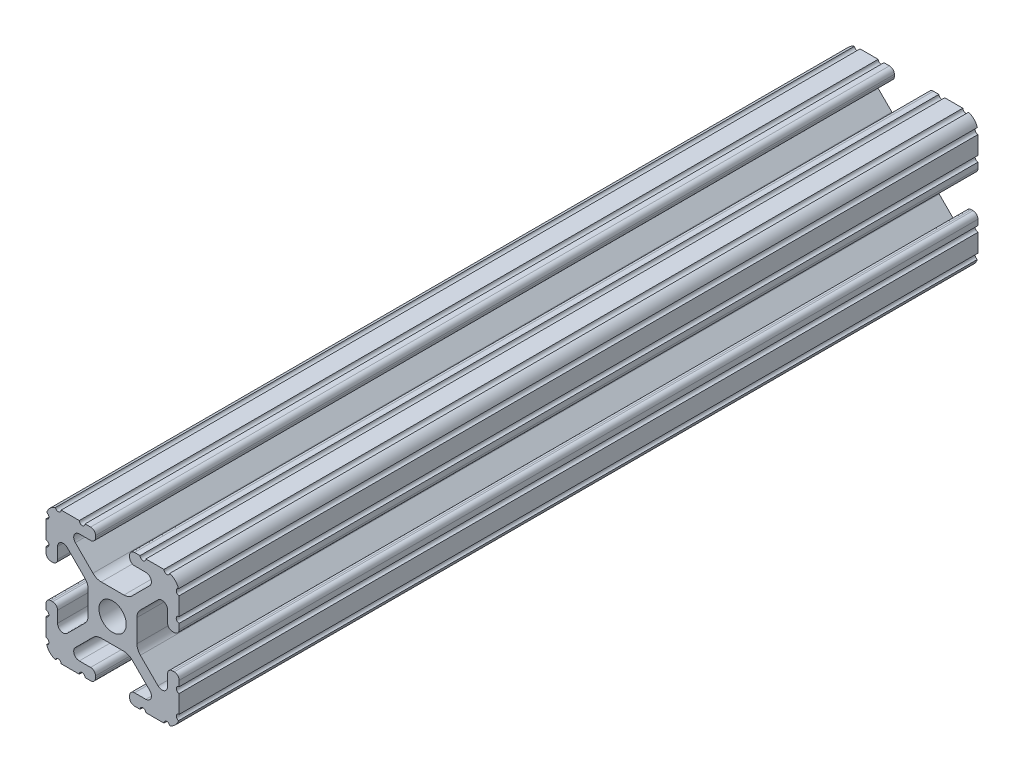
SolidWorks part; units mm, degrees
ref_plane "Front Plane" through (0, 0, 0) normal (0, 0, 1) x (1, 0, 0)
ref_plane "Top Plane" through (0, 0, 0) normal (0, 1, 0) x (1, 0, 0)
ref_plane "Right Plane" through (0, 0, 0) normal (1, 0, 0) x (0, 0, -1)
sketch "Sketch2" plane through (0, 0, 0) normal (0, 0, 1) x (1, 0, 0)
  line L0 (0, 12.7) -> (0, -12.7) construction
  line L1 (-12.7, 0) -> (12.7, 0) construction
  line L2 (3.2512, -12.7) -> (12.7, -12.7)
  line L3 (12.7, -12.7) -> (12.7, -3.2512)
  line L4 (3.2512, -12.7) -> (3.2512, -10.4902)
  line L5 (3.2512, -10.4902) -> (8.9276, -10.4902)
  line L6 (8.9276, -10.4902) -> (3.0856, -4.6482)
  line L7 (0, 0) -> (12.7, -12.7) construction
  line L8 (12.7, -3.2512) -> (10.4902, -3.2512)
  line L9 (10.4902, -3.2512) -> (10.4902, -8.9276)
  line L10 (10.4902, -8.9276) -> (4.6482, -3.0856)
  circle A0 centre (0, 0) radius 2.6035
  arc A1 (6.3485, -10.4902) -> (7.1039, -8.6665) centre (6.3485, -9.4219) ccw construction
  point P8 (0, -4.6482)
  dimension "Center Hole Diameter" = 5.207
  dimension "Rail Height" = 25.4
  dimension "Rail Width" = 25.4
  dimension "T-Slot Width" = 6.5024
  dimension "Slot Inner Width" = 14.8336
  dimension "Thickness" = 2.2098
  dimension "Slot Depth" = 5.842
  dimension "D1" = 2.2098
sketch "Sketch3" plane through (0, 0, 0) normal (1, 0, 0) x (0, 0, -1)
  line L0 (-76.2, -12.7) -> (76.2, -12.7) construction
  line L1 (-68.58, 0) -> (68.58, 0) construction
  dimension "Length" = 152.4
  dimension "D1" = 137.16
sketch "Sketch4" plane through (0, 0, 0) normal (0, 0, 1) x (1, 0, 0)
  line L0 (4.1904, -12.7) -> (10.1173, -12.7)
  line L1 (3.2512, -12.7) -> (12.7, -12.7) construction
  line L2 (3.2512, -12.7) -> (3.2512, -10.4902) construction
  line L3 (3.2512, -10.4902) -> (8.9276, -10.4902) construction
  line L4 (3.2512, -11.4294) -> (3.2512, -11.7608)
  line L5 (4.1904, -10.4902) -> (6.3485, -10.4902)
  line L6 (0, -4.6482) -> (2.164, -4.6482)
  line L7 (8.9276, -10.4902) -> (3.0856, -4.6482) construction
  line L8 (3.7373, -5.2999) -> (7.1039, -8.6665)
  line L9 (12.7, -12.7) -> (12.7, -3.2512) construction
  line L10 (10.4902, -8.9276) -> (4.6482, -3.0856) construction
  line L11 (10.4902, -3.2512) -> (10.4902, -8.9276) construction
  line L12 (10.4902, -6.3485) -> (10.4902, -4.1904)
  line L13 (12.7, -3.2512) -> (10.4902, -3.2512) construction
  line L14 (11.4294, -3.2512) -> (11.7608, -3.2512)
  line L15 (12.7, -4.1904) -> (12.7, -10.1173)
  line L16 (8.6665, -7.1039) -> (5.2999, -3.7373)
  line L17 (4.6482, 0) -> (4.6482, -2.164)
  line L18 (-12.7, 0) -> (12.7, 0) construction
  line L19 (0, -4.6482) -> (0, -2.6035)
  line L20 (0, 12.7) -> (0, -12.7) construction
  line L21 (4.6482, 0) -> (2.6035, 0)
  arc A0 (3.2512, -11.7608) -> (4.1904, -12.7) centre (4.1904, -11.7608) ccw
  arc A2 (3.2512, -11.4294) -> (4.1904, -10.4902) centre (4.1904, -11.4294) cw
  arc A3 (6.3485, -10.4902) -> (7.1039, -8.6665) centre (6.3485, -9.4219) ccw
  arc A4 (2.164, -4.6482) -> (3.7373, -5.2999) centre (2.164, -6.8732) cw
  arc A5 (10.1173, -12.7) -> (12.7, -10.1173) centre (10.1173, -10.1173) ccw
  arc A6 (8.6665, -7.1039) -> (10.4902, -6.3485) centre (9.4219, -6.3485) ccw
  arc A7 (10.4902, -4.1904) -> (11.4294, -3.2512) centre (11.4294, -4.1904) cw
  arc A8 (11.7608, -3.2512) -> (12.7, -4.1904) centre (11.7608, -4.1904) cw
  arc A9 (5.2999, -3.7373) -> (4.6482, -2.164) centre (6.8732, -2.164) cw
  circle A10 centre (0, 0) radius 2.6035 construction
  arc A11 (0, -2.6035) -> (2.6035, 0) centre (0, 0) ccw
  dimension "D1" = 2.5827
  dimension "D2" = 2.225
  dimension "D3" = 0.9392
extrude "Boss-Extrude1" add sketch "Sketch4" along normal mid plane 152.4
sketch "Sketch5" plane through (0, 0, 0) normal (0, 0, 1) x (1, 0, 0)
  line L0 (3.2512, -12.7) -> (12.7, -12.7) construction
  line L1 (4.1904, -10.4902) -> (6.3485, -10.4902) construction
  line L3 (0, 0) -> (12.7, -12.7) construction
  line L4 (6.3485, -10.4902) -> (6.3485, -12.7) construction
  line L5 (8.9276, -10.4902) -> (3.0856, -4.6482) construction
  circle A0 centre (10.3562, -12.7) radius 0.5524
  circle A1 centre (5.796, -12.7) radius 0.5524
  circle A2 centre (12.7, -10.3562) radius 0.5524
  circle A3 centre (12.7, -5.796) radius 0.5524
  point P10 (5.2694, -10.4902)
  point P12 (9.4219, -6.3485)
  dimension "D1" = 1.1049
extrude "Cut-Extrude1" cut sketch "Sketch5" against normal through all both and the other way through all
mirror "Mirror1" about plane through (0, 0, 0) normal (1, 0, 0) of bodies 137 134
mirror "Mirror2" about plane through (0, 0, 0) normal (0, 1, 0) of bodies 135
sketch "Sketch6" plane through (0, 0, 0) normal (0, 1, 0) x (1, 0, 0)
  line L0 (0, 76.2) -> (0, 63.5) construction
  line L1 (0, -76.2) -> (0, -63.5) construction
  line L4 (2.164, 76.2) -> (-2.164, 76.2)
  line L5 (-2.164, 76.2) -> (-2.164, -76.2)
  line L6 (-2.164, -76.2) -> (2.164, -76.2)
  line L7 (2.164, -76.2) -> (2.164, 76.2)
  line L8 (2.164, 76.2) -> (-2.164, 76.2) construction
  line L9 (-2.164, 76.2) -> (-2.164, -76.2) construction
  line L10 (-2.164, -76.2) -> (2.164, -76.2) construction
  line L11 (2.164, -76.2) -> (2.164, 76.2) construction
  circle A0 centre (0, -63.5) radius 3.175
  circle A1 centre (0, 63.5) radius 3.175
  dimension "D2" = 12.7
  dimension "D3" = 6.35
  dimension "D1" = 0
extrude "Cut-Extrude2" cut sketch "Sketch6" against normal through all both and the other way through all
equation "\"D1@Boss-Extrude1\"=\"Length@Sketch3\""
equation "\"D1@Sketch2\"=\"Thickness@Sketch2\""
equation "\"D2@Sketch4\"=\"Slot Inner Width@Sketch2\"*0.15"
equation "\"D1@Sketch4\"=\"D3@Sketch4\"*2.75"
equation "\"D3@Sketch4\"=\"Thickness@Sketch2\"*0.425"
equation "\"D1@Sketch5\"=\"Thickness@Sketch2\"*0.5"
equation "\"D1@Sketch3\"=\"Length@Sketch3\"*0.9"
